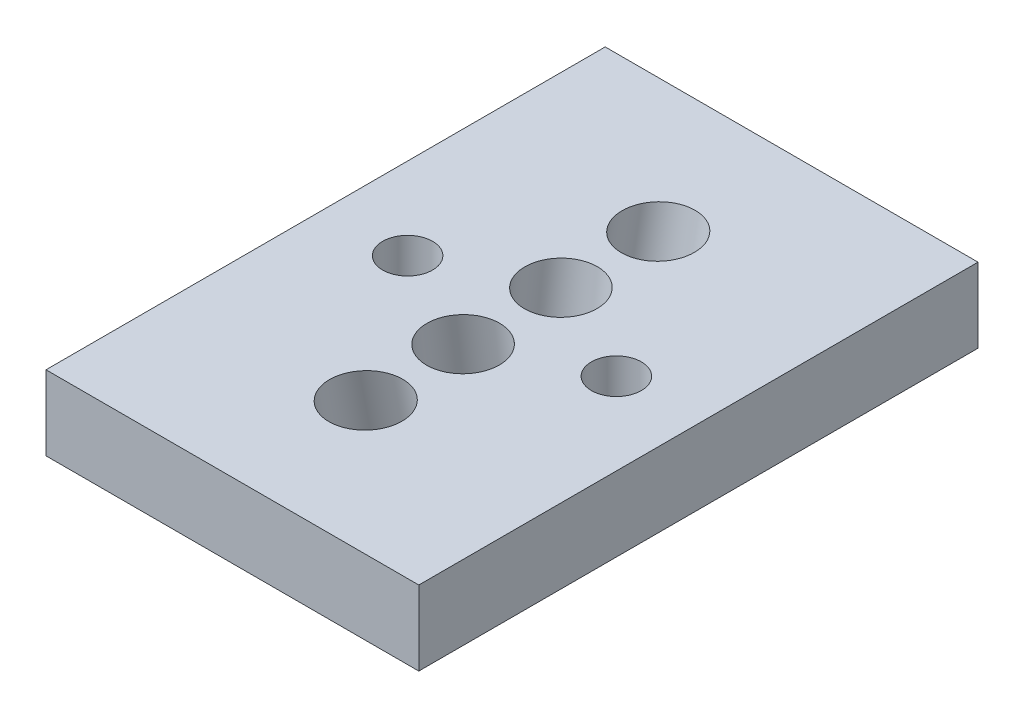
SolidWorks part; units mm, degrees
ref_plane "Front Plane" through (0, 0, 0) normal (0, 0, 1) x (1, 0, 0)
ref_plane "Top Plane" through (0, 0, 0) normal (0, 1, 0) x (1, 0, 0)
ref_plane "Right Plane" through (0, 0, 0) normal (1, 0, 0) x (0, 0, -1)
sketch "Sketch2" plane through (0, 0, 0) normal (0, 1, 0) x (1, 0, 0)
  line L1 (12.7, -19.05) -> (-12.7, -19.05)
  line L2 (12.7, -19.05) -> (12.7, 19.05)
  line L3 (12.7, 19.05) -> (-12.7, 19.05)
  line L4 (-12.7, -19.05) -> (-12.7, 19.05)
  line L5 (12.7, -19.05) -> (-12.7, 19.05) construction
  line L6 (12.7, 19.05) -> (-12.7, -19.05) construction
  point P0 (0, 0)
  dimension "D1" = 25.4
  dimension "D2" = 38.1
extrude "Boss-Extrude1" add sketch "Sketch2" along normal blind 5.08
sketch "Sketch6" plane through (12.7, 0, 0) normal (1, 0, 0) x (0, 0, -1)
  line L0 (-19.05, 124.7522) -> (-4.3561, 5.08) construction
  line L2 (-19.05, 5.08) -> (-19.05, 0) construction
  line L3 (-19.05, 5.08) -> (19.05, 5.08) construction
  line L4 (-4.3561, 5.08) -> (-4.3561, 22.1341) construction
  line L5 (-13.0683, 5.08) -> (-13.0683, 23.1616)
  line L6 (-13.0683, 5.08) -> (-16.6531, 23.776)
  dimension "D1" = 7
  dimension "D2" = 4.3561
  dimension "D3" = 5.9817
ref_plane "Plane3" through (12.7, 5.08, 4.3561) normal (0, -0.9925, -0.1219) x (-1, 0, 0)
sketch "Sketch7" plane through (12.7, 5.08, 4.3561) normal (0, -0.9925, -0.1219) x (-1, 0, 0)
  circle A0 centre (12.7, 1.016) radius 2.4638
extrude "Cut-Extrude1" cut sketch "Sketch7" along normal through all and the other way through all
ref_plane "Plane4" through (0, 0, 0) normal (0, 0, -1) x (-1, 0, 0)
ref_plane "Plane5" through (12.7, 5.08, 13.0683) normal (0, 0.9821, 0.1883) x (1, 0, 0)
sketch "Sketch16" plane through (12.7, 5.08, 13.0683) normal (0, 0.9821, 0.1883) x (1, 0, 0)
  circle A0 centre (-12.7, 3.048) radius 2.4638
extrude "Cut-Extrude2" cut sketch "Sketch16" against normal through all and the other way through all
mirror "Mirror2" about plane through (0, 0, 0) normal (0, 0, -1) of "Cut-Extrude1", "Cut-Extrude2"
hole_wizard "M3 Clearance Hole1" positions "Sketch21" profile "Sketch20" hole size "M3" standard "ANSI Metric"
sketch "Sketch21" plane through (0, 5.08, 0) normal (0, 1, 0) x (1, 0, 0)
  line L0 (2.794, 0) -> (-2.794, 0) construction
  line L1 (-12.7, 19.05) -> (-12.7, -19.05) construction
  line L2 (12.7, -19.05) -> (12.7, 19.05) construction
  point P0 (7.112, 0)
  point P4 (-7.112, 0)
  dimension "D1" = 5.588
  dimension "D2" = 5.588
sketch "Sketch20" plane through (7.112, 5.08, 0) normal (1, 0, 0) x (0, 0, 1)
  line L0 (0, 0) -> (0, 26.4215)
  line L1 (0, 26.4215) -> (1.7, 25.4)
  line L2 (1.7, 25.4) -> (1.7, 0)
  line L5 (1.7, 0) -> (0, 0)
  line L10 (0, 26.4215) -> (-1.7, 25.4) construction
  line L11 (0, -6.35) -> (0, 107.95) construction
  dimension "Hole Dia." = 3.4
  dimension "Hole Depth" = 25.4
  dimension "Drill Angle" = 118
sketch "Sketch17" plane through (0, 5.08, 0) normal (0, 1, 0) x (1, 0, 0)
  circle A0 centre (7.112, 0) radius 2.159
  circle A1 centre (-7.112, 0) radius 2.159
extrude "Cut-Extrude3" [suppressed] cut sketch "Sketch17" against normal through all
